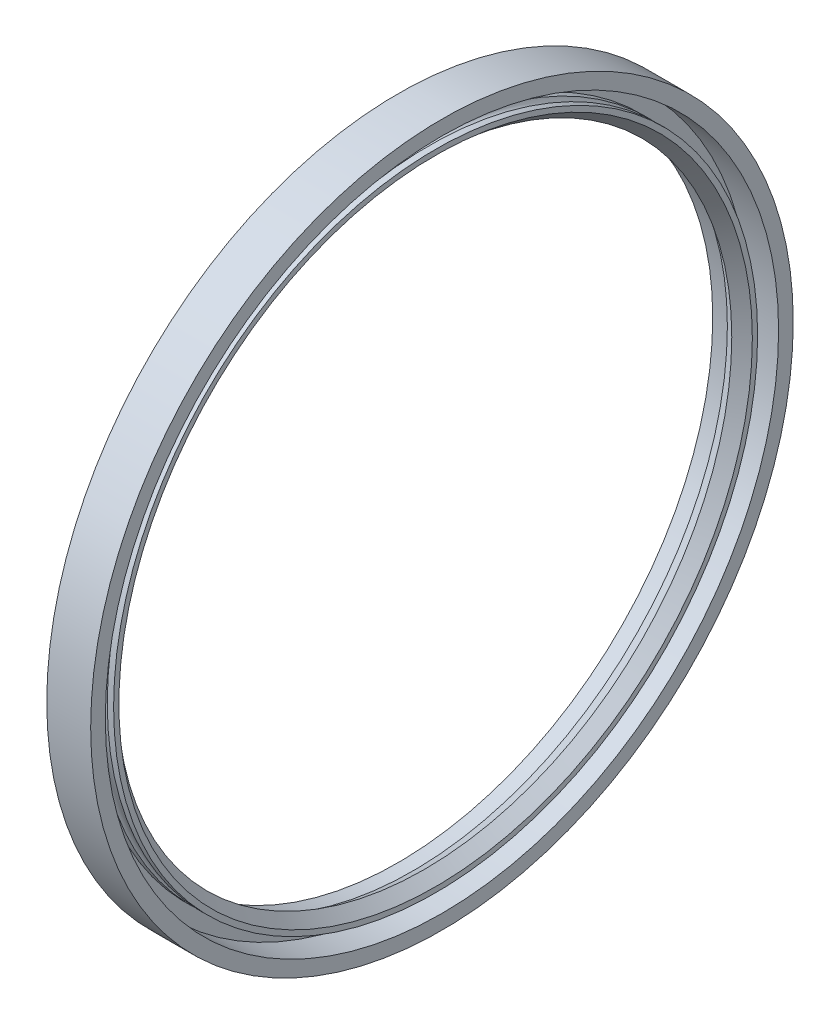
SolidWorks part; units mm, degrees
ref_plane "Front" through (0, 0, 0) normal (0, 0, 1) x (1, 0, 0)
ref_plane "Top" through (0, 0, 0) normal (0, 1, 0) x (1, 0, 0)
ref_plane "Right" through (0, 0, 0) normal (1, 0, 0) x (0, 0, -1)
sketch "Sketch1" plane through (0, 0, 0) normal (0, 0, 1) x (1, 0, 0)
  line L0 (15, 120) -> (0, 120)
  line L1 (0, 120) -> (0, 107.5)
  line L2 (0, 107.5) -> (5, 107.5)
  line L3 (5, 107.5) -> (9, 105)
  line L4 (9, 105) -> (12.8333, 108.1944)
  line L5 (12.8333, 108.1944) -> (12.8333, 110)
  line L6 (12.8333, 110) -> (10.6667, 110)
  line L7 (7.3333, 110) -> (5, 110)
  line L8 (5, 110) -> (5, 115)
  line L9 (5, 115) -> (15, 115)
  line L10 (15, 115) -> (15, 120)
  line L11 (-0.005, 0) -> (15.005, 0) construction
  arc A0 (7.3333, 110) -> (10.6667, 110) centre (9, 110) ccw
  dimension "D1" = 1.6667
  dimension "D2" = 110
revolve "Revolve1" add sketch "Sketch1" angle 360 about L11 reverse direction yes
ref_plane "Plane1" through (9, 0, 0) normal (1, 0, 0) x (0, 0, -1)
ref_axis "Axis1" through (-80.9, 0, 0) along (1, 0, 0)
